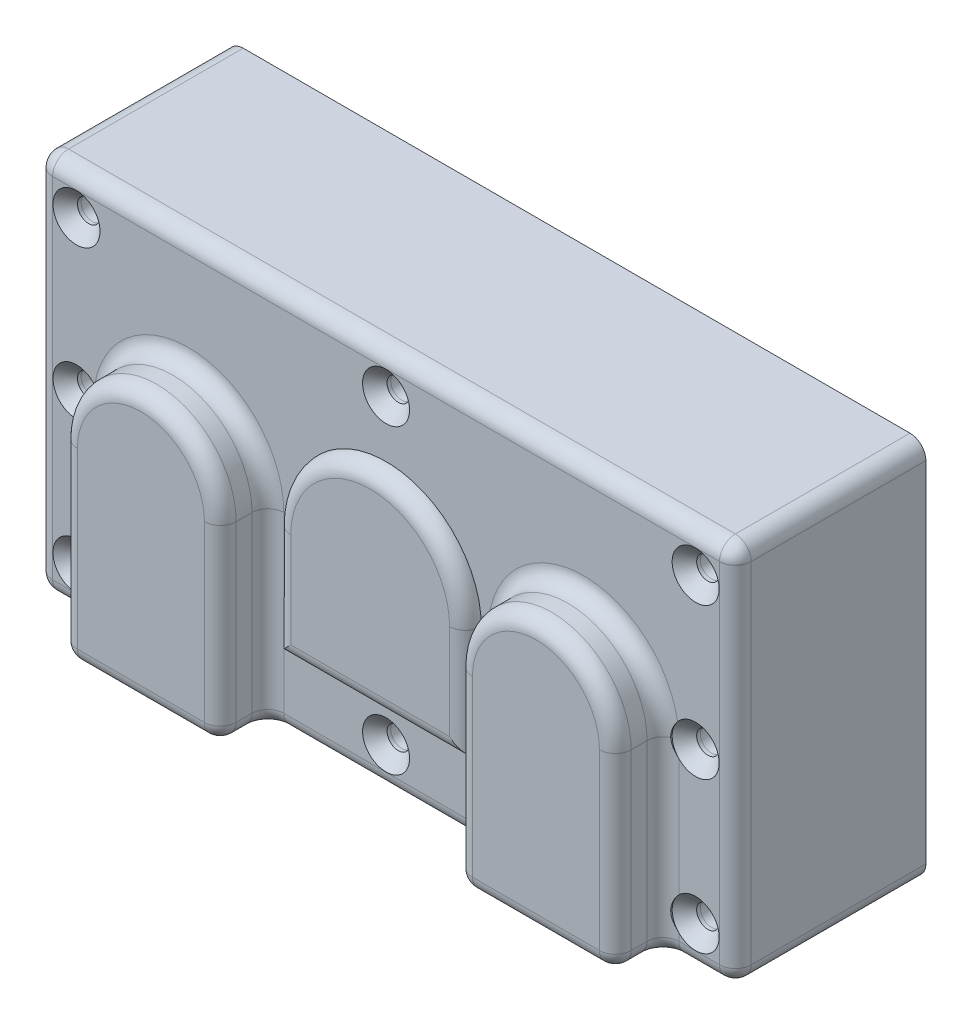
SolidWorks part; units mm, degrees
material "Custom Plastic"
ref_plane "X-Y Datum" through (0, 0, 0) normal (0, 0, 1) x (1, 0, 0)
ref_plane "X-Z Datum" through (0, 0, 0) normal (0, 1, 0) x (1, 0, 0)
ref_plane "Y-Z Datum" through (0, 0, 0) normal (1, 0, 0) x (0, 0, -1)
sketch "Sketch3" plane through (0, 0, 0) normal (0, 0, 1) x (1, 0, 0)
  line L1 (-69.85, 38.1) -> (69.85, 38.1)
  line L2 (-69.85, 38.1) -> (-69.85, -38.1)
  line L3 (-69.85, -38.1) -> (69.85, -38.1)
  line L4 (69.85, 38.1) -> (69.85, -38.1)
  line L5 (-69.85, 38.1) -> (69.85, -38.1) construction
  line L6 (-69.85, -38.1) -> (69.85, 38.1) construction
  point P0 (0, 0)
  dimension "D1" = 139.7
  dimension "D2" = 76.2
extrude "Boss-Extrude1" add sketch "Sketch3" along normal blind 38.1
ref_plane "Plane1" through (0, 0, 0) normal (0, -1, 0) x (-1, 0, 0)
sketch "Sketch13" plane through (0, 0, 38.1) normal (0, 0, 1) x (1, 0, 0)
  line L0 (-69.85, -0.1574) -> (69.85, -0.1574) construction
  line L1 (-69.85, 38.1) -> (-69.85, -38.1) construction
  line L2 (69.85, -38.1) -> (69.85, 38.1) construction
  line L3 (0, 38.1) -> (0, -38.1) construction
  line L4 (69.85, 38.1) -> (-69.85, 38.1) construction
  line L5 (-69.85, -38.1) -> (69.85, -38.1) construction
  line L6 (23.6247, -0.1574) -> (23.6247, -38.1)
  line L7 (-55.3747, -0.1574) -> (-23.6247, -0.1574) construction
  line L8 (-55.3747, -0.1574) -> (-55.3747, -38.1)
  line L9 (-55.3747, -38.1) -> (-23.6247, -38.1)
  line L10 (-23.6247, -0.1574) -> (-23.6247, -38.1)
  line L11 (55.3747, -0.1574) -> (55.3747, -38.1)
  line L12 (55.3747, -38.1) -> (23.6247, -38.1)
  line L13 (-19.05, -0.1574) -> (19.05, -0.1574) construction
  line L14 (-19.05, -0.1574) -> (-19.05, -22.3824)
  line L15 (19.05, -0.1574) -> (19.05, -22.3824)
  line L16 (-19.05, -22.3824) -> (19.05, -22.3824)
  circle A0 centre (-39.4997, -0.1574) radius 15.875 construction
  arc A1 (-55.3747, -0.1574) -> (-23.6247, -0.1574) centre (-39.4997, -0.1574) cw
  arc A2 (55.3747, -0.1574) -> (23.6247, -0.1574) centre (39.4997, -0.1574) ccw
  circle A3 centre (0, -0.1574) radius 19.05 construction
  arc A4 (-19.05, -0.1574) -> (19.05, -0.1574) centre (0, -0.1574) cw
  circle A26 centre (-39.4997, -0.1574) radius 4.25 construction
  line M5 (-69.85, -38.1) -> (69.85, -38.1)
  dimension "D1" = 31.75
  dimension "D3" = 38.1
  dimension "D2" = 30.3503
  dimension "D4" = 22.225
extrude "Boss-Extrude3" add sketch "Sketch13" along normal blind 9.525 contours A1 L8 L10 M5 | L11 A2 L6 M5 region at (39.4997, -12.7701, 38.1) region at (-39.4997, -12.7701, 38.1)
extrude "Boss-Extrude4" add sketch "Sketch13<3>" along normal blind 3.175 contours A4 L14 L16 L15 region at (0, -3.5459, 38.1)
sketch "Sketch13<3>" plane through (0, 0, 38.1) normal (0, 0, 1) x (1, 0, 0) same geometry as "Sketch13"
shell "Shell1" thickness 5.08 removed face at (0, 0, 0)
sketch "Sketch9" plane through (0, 0, 0) normal (0, 0, 1) x (1, 0, 0)
  line L1 (-69.85, 38.1) -> (-69.85, -38.1) construction
  line L2 (0, 38.1) -> (0, -38.1) construction
  line L3 (69.85, 38.1) -> (-69.85, 38.1) construction
  line L4 (-69.85, 0) -> (69.85, 0) construction
  line L5 (69.85, -38.1) -> (69.85, 38.1) construction
  line L6 (-4.0411, 30.1625) -> (4.0411, 30.1625) construction
  line L7 (-4.0411, 38.1) -> (4.0411, 38.1)
  line L8 (-61.9125, 4.0411) -> (-61.9125, -4.0411) construction
  line L9 (-61.9125, 4.0411) -> (-69.85, 4.0411)
  line L10 (-61.9125, -4.0411) -> (-69.85, -4.0411)
  line L11 (-69.85, 4.0411) -> (-69.85, -4.0411)
  line L12 (-69.85, 38.1) -> (-69.85, -38.1) construction
  line L13 (-4.0411, -30.1625) -> (4.0411, -30.1625) construction
  line L14 (-4.0411, -30.1625) -> (-4.0411, -38.1)
  line L15 (4.0411, -30.1625) -> (4.0411, -38.1)
  line L16 (-4.0411, -38.1) -> (4.0411, -38.1)
  line L17 (-69.85, -38.1) -> (-55.3747, -38.1) construction
  line L18 (4.0411, 30.1625) -> (4.0411, 38.1)
  line L19 (-4.0411, 30.1625) -> (-4.0411, 38.1)
  line L20 (61.9125, 4.0411) -> (61.9125, -4.0411) construction
  line L21 (69.85, 4.0411) -> (69.85, -4.0411)
  line L22 (61.9125, -4.0411) -> (69.85, -4.0411)
  line L23 (61.9125, 4.0411) -> (69.85, 4.0411)
  line L25 (-55.3747, -38.1) -> (-23.6247, -38.1) construction
  circle A0 centre (-61.9125, -30.1625) radius 7.9375 construction
  circle A1 centre (-61.9125, 30.1625) radius 7.9375 construction
  circle A2 centre (61.9125, -30.1625) radius 7.9375 construction
  circle A3 centre (61.9125, 30.1625) radius 7.9375 construction
  circle A4 centre (-61.9125, 0) radius 7.9375 construction
  circle A5 centre (0, 30.1625) radius 7.9375 construction
  circle A6 centre (61.9125, 0) radius 7.9375 construction
  circle A7 centre (0, -30.1625) radius 7.9375 construction
  circle A9 centre (-61.9125, -30.1625) radius 4.0411
  circle A10 centre (-61.9125, 0) radius 4.0411 construction
  circle A13 centre (-61.9125, 30.1625) radius 4.0411
  circle A14 centre (61.9125, -30.1625) radius 4.0411
  circle A16 centre (61.9125, 30.1625) radius 4.0411
  circle A17 centre (0, -30.1625) radius 4.0411 construction
  arc A18 (-61.9125, 4.0411) -> (-61.9125, -4.0411) centre (-61.9125, 0) cw
  arc A19 (-4.0411, -30.1625) -> (4.0411, -30.1625) centre (0, -30.1625) cw
  circle A20 centre (0, 30.1625) radius 4.0411 construction
  arc A21 (-4.0411, 30.1625) -> (4.0411, 30.1625) centre (0, 30.1625) ccw
  circle A22 centre (61.9125, 0) radius 4.0411 construction
  arc A23 (61.9125, 4.0411) -> (61.9125, -4.0411) centre (61.9125, 0) ccw
  dimension "D1" = 15.875
extrude "Boss-Extrude2" add sketch "Sketch9" along normal up to surface (38.1 mm away) up to face at (0, -6.5074, 38.1)
sketch "Sketch6" plane through (0, 0, 0) normal (0, -1, 0) x (1, 0, 0)
  line L0 (-69.85, 0) -> (-64.77, 0) construction
  line L1 (-69.85, 0) -> (69.85, 0) construction
  line L2 (-68.6435, 1.3208) -> (-65.9765, 1.3208)
  line L3 (-67.31, 1.3208) -> (-67.31, 0) construction
  line L4 (-68.6435, 1.3208) -> (-68.7012, 0)
  line L7 (-65.9765, 1.3208) -> (-65.9188, 0)
  arc A0 (-68.7012, 0) -> (-65.9188, 0) centre (-67.31, 0.1064) ccw
  dimension "D1" = 5.08
  dimension "D2" = 1.3208
  dimension "D3" = 2.667
  dimension "D4" = 92.5
sketch "Sketch7" plane through (0, 0, 0) normal (0, 0, -1) x (-1, 0, 0)
  line L0 (-69.85, 38.1) -> (69.85, 38.1) construction
  line L1 (-64.77, 35.56) -> (64.77, 35.56)
  line L2 (-67.31, 33.02) -> (-67.31, -33.02)
  line L3 (-64.77, -35.56) -> (64.77, -35.56)
  line L4 (67.31, 33.02) -> (67.31, -33.02)
  line L6 (-69.85, -38.1) -> (-69.85, 38.1) construction
  line L7 (69.85, 38.1) -> (69.85, -38.1) construction
  line L9 (69.85, -38.1) -> (-69.85, -38.1) construction
  arc A0 (64.77, 35.56) -> (67.31, 33.02) centre (64.77, 33.02) cw
  arc A1 (64.77, -35.56) -> (67.31, -33.02) centre (64.77, -33.02) ccw
  arc A2 (-67.31, -33.02) -> (-64.77, -35.56) centre (-64.77, -33.02) ccw
  arc A3 (-64.77, 35.56) -> (-67.31, 33.02) centre (-64.77, 33.02) ccw
  point P21 (67.31, -33.02)
  dimension "D6" = 2.54
  dimension "D1" = 2.54
  dimension "D2" = 2.54
  dimension "D3" = 2.54
  dimension "D4" = 2.54
sweep "O Ring Cut" cut profiles "Sketch6" path "Sketch7"
fillet "Fillet2" radius 3.175 32 edges at (23.6247, -38.1, 42.8625) (55.3747, -38.1, 42.8625) (0, -38.1, 38.1) (62.6123, -38.1, 38.1) (-62.6123, -38.1, 38.1) (-69.85, 0, 38.1) (0, 38.1, 38.1) (55.3747, -19.1287, 38.1) (23.6247, -19.1287, 38.1) (55.3747, -19.1287, 47.625) (23.6247, -19.1287, 47.625) (-55.3747, -19.1287, 47.625) (-23.6247, -19.1287, 47.625) (-55.3747, -19.1287, 38.1) (-39.4997, 15.7176, 38.1) (39.4997, -38.1, 47.625) (-39.4997, -38.1, 47.625) (-23.6247, -38.1, 42.8625) (-55.3747, -38.1, 42.8625) (69.85, 0, 38.1) (39.4997, 15.7176, 38.1) (39.4997, 15.7176, 47.625) (-39.4997, 15.7176, 47.625) (-23.6247, -19.1287, 38.1) (19.05, -11.2699, 41.275) (0, -22.3824, 41.275) (-19.05, -11.2699, 41.275) (0, 18.8926, 41.275) (-69.85, -38.1, 19.05) (-69.85, 38.1, 19.05) (69.85, 38.1, 19.05) (69.85, -38.1, 19.05)
hole_wizard "M4 Clearance Hole1" positions "Sketch10" profile "Sketch11" hole size "M4" standard "ANSI Metric"
sketch "Sketch10" plane through (0, 0, 0) normal (0, 0, -1) x (-1, 0, 0)
  point P0 (-61.9125, 0)
  point P3 (-61.9125, 30.1625)
  point P6 (0, 30.1625)
  point P9 (61.9125, 30.1625)
  point P12 (61.9125, 0)
  point P15 (61.9125, -30.1625)
  point P18 (0, -30.1625)
  point P21 (-61.9125, -30.1625)
sketch "Sketch11" plane through (61.9125, 0, 0) normal (1, 0, 0) x (0, 1, 0)
  line L0 (0, 0) -> (0, 13.3519)
  line L1 (0, 13.3519) -> (2.25, 12)
  line L2 (2.25, 12) -> (2.25, 0.025)
  line L3 (2.25, 0.025) -> (2.275, 0)
  line L5 (2.275, 0) -> (0, 0)
  line L6 (-2.25, 0.025) -> (-2.275, 0) construction
  line L10 (0, 13.3519) -> (-2.25, 12) construction
  line L11 (0, -6.35) -> (0, 107.95) construction
  dimension "Hole Dia." = 4.5
  dimension "Hole Depth" = 12
  dimension "Near C'Sink Dia." = 4.55
  dimension "Near C'Sink Angle" = 90
  dimension "Drill Angle" = 118
hole_wizard "CSK for M4 Flat Head Machine Screw1" positions "Sketch16" profile "Sketch17" countersink size "M4" standard "ANSI Metric"
sketch "Sketch16" plane through (0, 0, 38.1) normal (0, 0, 1) x (1, 0, 0)
  point P0 (-61.9125, 30.1625)
  point P3 (0, 30.1625)
  point P6 (61.9125, 30.1625)
  point P9 (61.9125, 0)
  point P12 (61.9125, -30.1625)
  point P15 (0, -30.1625)
  point P18 (-61.9125, -30.1625)
  point P21 (-61.9125, 0)
sketch "Sketch17" plane through (-61.9125, 30.1625, 38.1) normal (1, 0, 0) x (0, -1, 0)
  line L0 (0, 0) -> (0, 13.3519)
  line L1 (0, 13.3519) -> (2.25, 12)
  line L2 (2.25, 12) -> (2.25, 2.45)
  line L3 (2.25, 2.45) -> (4.7, 0)
  line L5 (4.7, 0) -> (0, 0)
  line L6 (-2.25, 2.45) -> (-4.7, 0) construction
  line L10 (0, 13.3519) -> (-2.25, 12) construction
  line L11 (0, -6.35) -> (0, 107.95) construction
  dimension "Hole Dia." = 4.5
  dimension "Hole Depth" = 12
  dimension "Near C'Sink Dia." = 9.4
  dimension "Near C'Sink Angle" = 90
  dimension "Drill Angle" = 118
sketch "Sketch15" plane through (0, -38.1, 0) normal (0, -1, 0) x (1, 0, 0)
  circle A0 centre (-39.4997, 34.6) radius 6.35
  circle A1 centre (39.4997, 34.6) radius 6.35
  circle A2 centre (-39.4997, 34.6) radius 4.5 construction
  circle A3 centre (39.4997, 34.6) radius 4.5 construction
  dimension "D1" = 12.7
  dimension "D2" = 12.7
extrude "Cut-Extrude1" cut sketch "Sketch15" against normal up to surface (5.08 mm away) up to face at (-35.5239, -33.02, 27.1463)
ref_plane "Cut Plane" through (0, 0, 34.925) normal (0, 0, -1) x (-1, 0, 0)
sketch "Sketch19" plane through (0, -38.1, 0) normal (0, -1, 0) x (1, 0, 0)
  line L0 (-66.675, 9.525) -> (66.675, 9.525) construction
  line L3 (-66.675, 34.925) -> (-66.675, 0) construction
  line L4 (66.675, 0) -> (66.675, 34.925) construction
  line L5 (-66.675, 0) -> (66.675, 0) construction
  text T0 "HVD" font "Century Gothic" height 19.05
  dimension "D1" = 9.525
extrude "HVD text" cut sketch "Sketch19" against normal blind 1.5875
sketch "Sketch22" plane through (-69.85, 0, 0) normal (-1, 0, 0) x (0, 0, 1)
  line L0 (9.525, -38.1) -> (9.525, 34.925) construction
  line L1 (34.925, 34.925) -> (0, 34.925) construction
  text T0 "<b>HVD</b>" font "Century Gothic" height 19.05
extrude "HVD text top" cut sketch "Sketch22" against normal blind 1.5875
sketch "Sketch21" plane through (0, 0, 38.1) normal (0, 0, 1) x (1, 0, 0)
  circle A0 centre (-61.9125, -30.1625) radius 4.7
  circle A1 centre (-61.9125, 0) radius 4.7
  circle A2 centre (61.9125, -30.1625) radius 4.7
  circle A3 centre (61.9125, 0) radius 4.7
  arc A4 (-58.2876, 2.9917) -> (-58.5497, -3.2835) centre (-61.9125, 0) ccw construction
  arc A5 (-58.5497, -26.879) -> (-58.5497, -33.446) centre (-61.9125, -30.1625) ccw construction
  arc A6 (58.5497, -33.446) -> (58.5497, -26.879) centre (61.9125, -30.1625) ccw construction
  arc A7 (58.5497, -3.2835) -> (58.2876, 2.9917) centre (61.9125, 0) ccw construction
extrude "Cut-Extrude4" cut sketch "Sketch21" along normal through all
split "Split2" trim tools "Cut Plane" bodies to split 113 resulting bodies 116 117
equation "\"shell width\"= 0.2"
equation "\"D1@Shell1\"=\"shell width\""
equation "\"D1@Sketch6\"=\"shell width\""
equation "\"D1@Sketch7\"=\"shell width\"/2"
equation "\"D2@Sketch7\"=\"shell width\"/2"
equation "\"D3@Sketch7\"=\"shell width\"/2"
equation "\"D4@Sketch7\"=\"shell width\"/2"
equation "\"D6@Sketch7\"=\"shell width\"/2"
